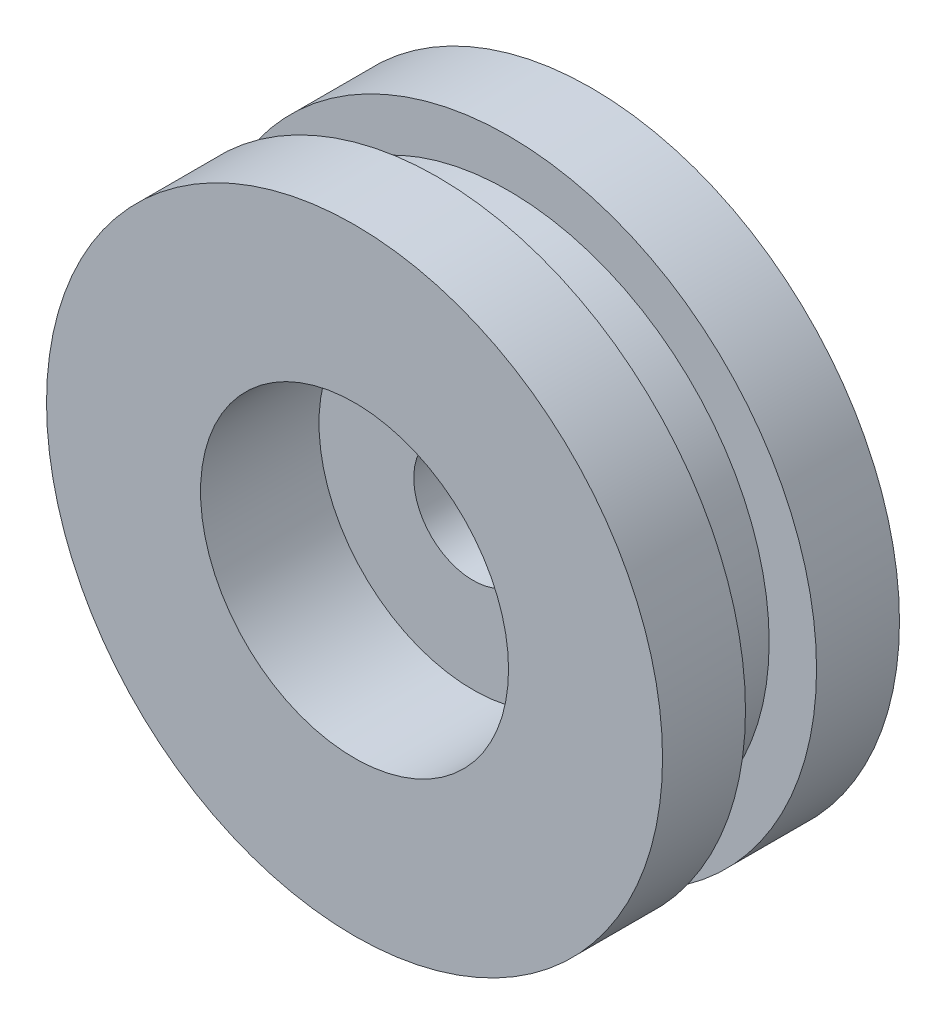
SolidWorks part; units mm, degrees
material "Gray Cast Iron (SN)"
ref_plane "Front Plane" through (0, 0, 0) normal (0, 0, 1) x (1, 0, 0)
ref_plane "Top Plane" through (0, 0, 0) normal (0, 1, 0) x (1, 0, 0)
ref_plane "Right Plane" through (0, 0, 0) normal (1, 0, 0) x (0, 0, -1)
sketch "Sketch1" plane through (0, 0, 0) normal (0, 0, 1) x (1, 0, 0)
  circle A0 centre (0, 0) radius 13
  circle A1 centre (0, 0) radius 11
  circle A2 centre (0, 0) radius 6.5
  circle A3 centre (0, 0) radius 2.5
  dimension "D1" = 26
  dimension "D2" = 22
  dimension "D3" = 5
  dimension "13" = 13
extrude "Boss-Extrude1" add sketch "Sketch1" along normal mid plane 10 contours A1 A2 region at (-10.6889, 0, 0)
extrude "Boss-Extrude2" add sketch "Sketch1<3>" along normal blind 3.5 from offset 1.5 contours A0 A1 region at (-12.6323, 0, 0)
sketch "Sketch1<3>" plane through (0, 0, 0) normal (0, 0, 1) x (1, 0, 0) same geometry as "Sketch1"
extrude "Boss-Extrude3" add sketch "Sketch1<5>" against normal blind 5 contours A2 A3 region at (-6.3162, 0, 0)
sketch "Sketch1<5>" plane through (0, 0, 0) normal (0, 0, 1) x (1, 0, 0) same geometry as "Sketch1"
cosmetic thread "Cosmetic Thread1" parameters "D2"=6
extrude "Boss-Extrude4" add sketch "Sketch1<6>" against normal blind 3.5 from offset 1.5 contours A0 A1 region at (-12.6323, 0, 0) offset against normal yes
sketch "Sketch1<6>" plane through (0, 0, 0) normal (0, 0, 1) x (1, 0, 0) same geometry as "Sketch1"
